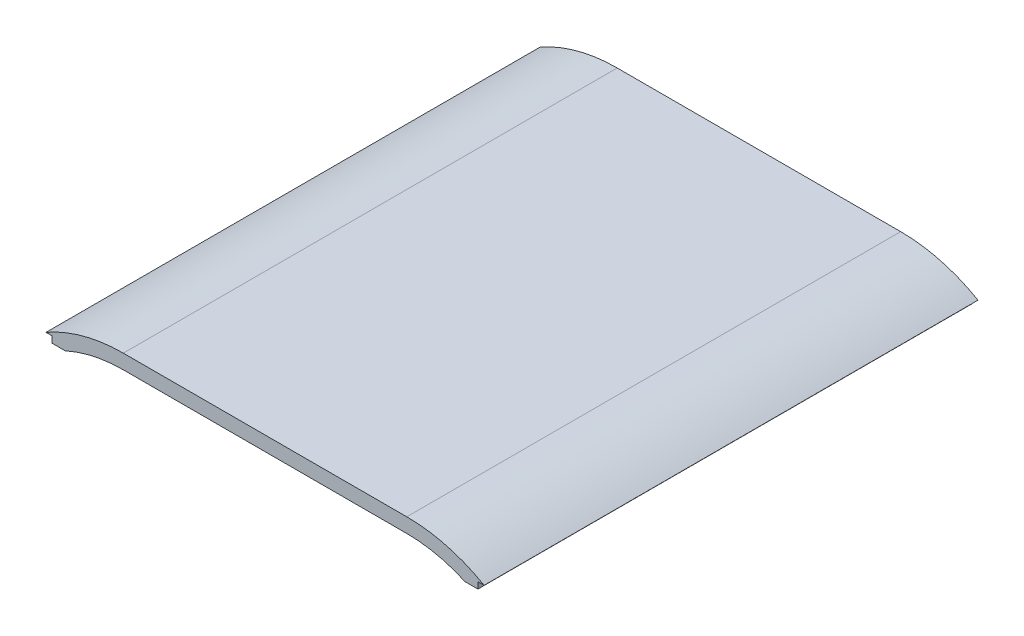
SolidWorks part; units mm, degrees
material "that blue high density foam"
ref_plane "Front" through (0, 0, 0) normal (0, 0, 1) x (1, 0, 0)
ref_plane "Top" through (0, 0, 0) normal (0, 1, 0) x (1, 0, 0)
ref_plane "Right" through (0, 0, 0) normal (1, 0, 0) x (0, 0, -1)
sketch "Sketch1" plane through (0, 0, 0) normal (0, 0, 1) x (1, 0, 0)
  line L1 (-68.5834, 162.2134) -> (68.5834, 162.2134)
  line L2 (-106, 152.2134) -> (-103, 152.2134)
  line L4 (-68.5834, 155.2134) -> (68.5834, 155.2134)
  line L5 (-96.7213, 149.1187) -> (-96.7213, 149.1187)
  line L6 (103, 152.2134) -> (106, 152.2134)
  line L7 (-96.7213, 149.1187) -> (-103, 149.1187)
  line L9 (-103, 149.1187) -> (-103, 152.2134)
  line L13 (0, 169.0467) -> (0, 139.3264) construction
  line L14 (96.7213, 149.1187) -> (103, 149.1187)
  line L15 (103, 149.1187) -> (103, 152.2134)
  arc A0 (-68.5834, 162.2134) -> (-106, 152.2134) centre (-68.5834, 87.2134) ccw construction
  arc A1 (-68.5834, 162.2134) -> (-106, 152.2134) centre (-68.5834, 87.2134) ccw
  arc A2 (106, 152.2134) -> (68.5834, 162.2134) centre (68.5834, 87.2134) ccw construction
  arc A3 (106, 152.2134) -> (68.5834, 162.2134) centre (68.5834, 87.2134) ccw
  arc A5 (-68.5834, 155.2134) -> (-96.7213, 149.1187) centre (-68.5834, 87.2134) ccw
  arc A6 (102.5078, 146.1468) -> (68.5834, 155.2134) centre (68.5834, 87.2134) ccw construction
  arc A7 (68.5834, 155.2134) -> (96.7213, 149.1187) centre (68.5834, 87.2134) cw
  point P22 (0, 0)
  dimension "D1" = 7
extrude "Boss-Extrude1" add sketch "Sketch1" along normal up to surface (239 mm away) contours A5 L4 L6 A3 L1 A1 L2 L9 L7 region at (0, 157.8037, 0)
